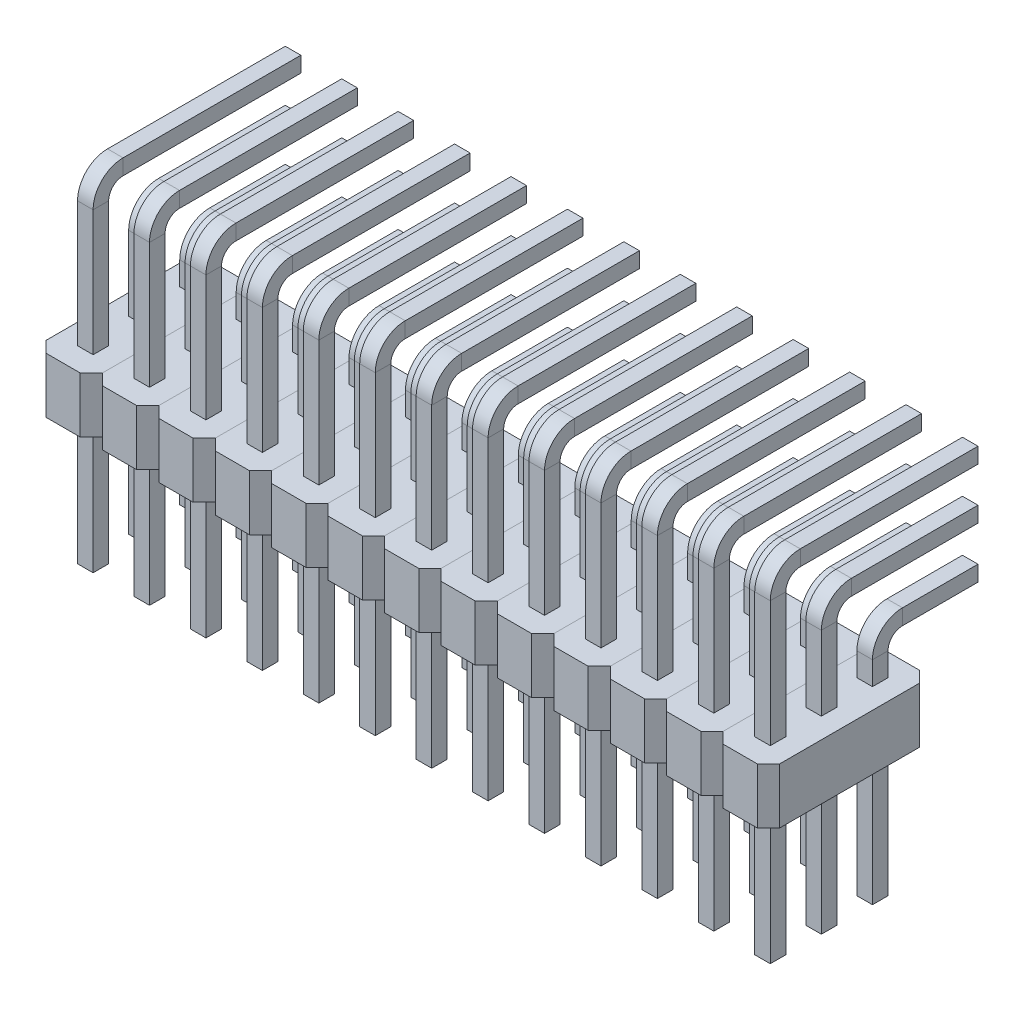
SolidWorks part; units mm, degrees
material "201 Annealed Stainless Steel (SS)"
ref_plane "Front Plane" through (0, 0, 0) normal (0, 0, 1) x (1, 0, 0)
ref_plane "Top Plane" through (0, 0, 0) normal (0, 1, 0) x (1, 0, 0)
ref_plane "Right Plane" through (0, 0, 0) normal (1, 0, 0) x (0, 0, -1)
sketch "Sketch1" plane through (0, 0, 0) normal (0, 1, 0) x (1, 0, 0)
  line L0 (0, 0) -> (2.54, 0)
  line L1 (0, 0) -> (0, -7.3)
  line L2 (0, -7.3) -> (2.54, -7.3)
  line L3 (2.54, 0) -> (2.54, -7.3)
  line L4 (0.92, -1) -> (1.62, -1)
  line L5 (0.92, -1) -> (0.92, -1.7)
  line L6 (0.92, -1.7) -> (1.62, -1.7)
  line L7 (1.62, -1) -> (1.62, -1.7)
  line L8 (0.92, -5.6) -> (1.62, -5.6)
  line L9 (0.92, -5.6) -> (0.92, -6.3)
  line L10 (0.92, -6.3) -> (1.62, -6.3)
  line L11 (1.62, -5.6) -> (1.62, -6.3)
  line L12 (0.92, -3.3) -> (1.62, -3.3)
  line L13 (0.92, -3.3) -> (0.92, -4)
  line L14 (0.92, -4) -> (1.62, -4)
  line L15 (1.62, -3.3) -> (1.62, -4)
  dimension "D1" = 7.3
  dimension "D2" = 2.54
  dimension "D3" = 0.92
  dimension "D4" = 1
  dimension "D5" = 0.7
  dimension "D6" = 1.6
  dimension "D7" = 1.6
ref_plane "Plane1" through (1.25, 0, 0) normal (1, 0, 0) x (0, 0, -1)
sketch "Sketch2" plane through (1.25, 0, 0) normal (1, 0, 0) x (0, 0, -1)
  line L0 (-5.95, 8.15) -> (-5.95, -6)
  line L1 (-3.65, 5.85) -> (-3.65, -6)
  line L2 (-1.35, 3.55) -> (-1.35, -6)
  line L3 (-4.95, 9.15) -> (3.05, 9.15)
  line L4 (0, 0) -> (-7.3, 0) construction
  line L5 (-2.65, 6.85) -> (3.05, 6.85)
  line L6 (-0.35, 4.55) -> (3.05, 4.55)
  arc A0 (-1.35, 3.55) -> (-0.35, 4.55) centre (-0.35, 3.55) cw
  arc A1 (-3.65, 5.85) -> (-2.65, 6.85) centre (-2.65, 5.85) cw
  arc A2 (-5.95, 8.15) -> (-4.95, 9.15) centre (-4.95, 8.15) cw
  point P19 (-5.95, 9.15)
  dimension "D9" = 1
  dimension "D1" = 15.15
  dimension "D2" = 2.3
  dimension "D3" = 2.3
  dimension "D4" = 1.35
  dimension "D5" = 6
  dimension "D6" = 9
  dimension "D7" = 2.3
  dimension "D8" = 2.3
sweep "Sweep3" add profiles "Sketch1" path "Sketch2"
sweep "Sweep4" add profiles "Sketch1<5>" path "Sketch2<6>"
sketch "Sketch1<5>" plane through (0, 0, 0) normal (0, 1, 0) x (1, 0, 0) same geometry as "Sketch1"
sketch "Sketch2<6>" plane through (1.25, 0, 0) normal (1, 0, 0) x (0, 0, -1) same geometry as "Sketch2"
sweep "Sweep5" add profiles "Sketch1<6>" path "Sketch2<7>"
sketch "Sketch1<6>" plane through (0, 0, 0) normal (0, 1, 0) x (1, 0, 0) same geometry as "Sketch1"
sketch "Sketch2<7>" plane through (1.25, 0, 0) normal (1, 0, 0) x (0, 0, -1) same geometry as "Sketch2"
extrude "Boss-Extrude1" add sketch "Sketch1<7>" along normal blind 2.5 contours L3 L0 L1 L2 L4 L7 L6 L5 L8 L11 L10 L9 L12 L15 L14 L13 region at (1.27, 0, 0.0773)
sketch "Sketch1<7>" plane through (0, 0, 0) normal (0, 1, 0) x (1, 0, 0) same geometry as "Sketch1"
chamfer "Chamfer1" distance 0.5 angle 45 4 edges at (0, 1.25, 0) (2.54, 1.25, 0) (0, 1.25, 7.3) (2.54, 1.25, 7.3)
pattern_linear "LPattern1" count 13 spacing 2.54 along (1, 0, 0) of bodies 104
